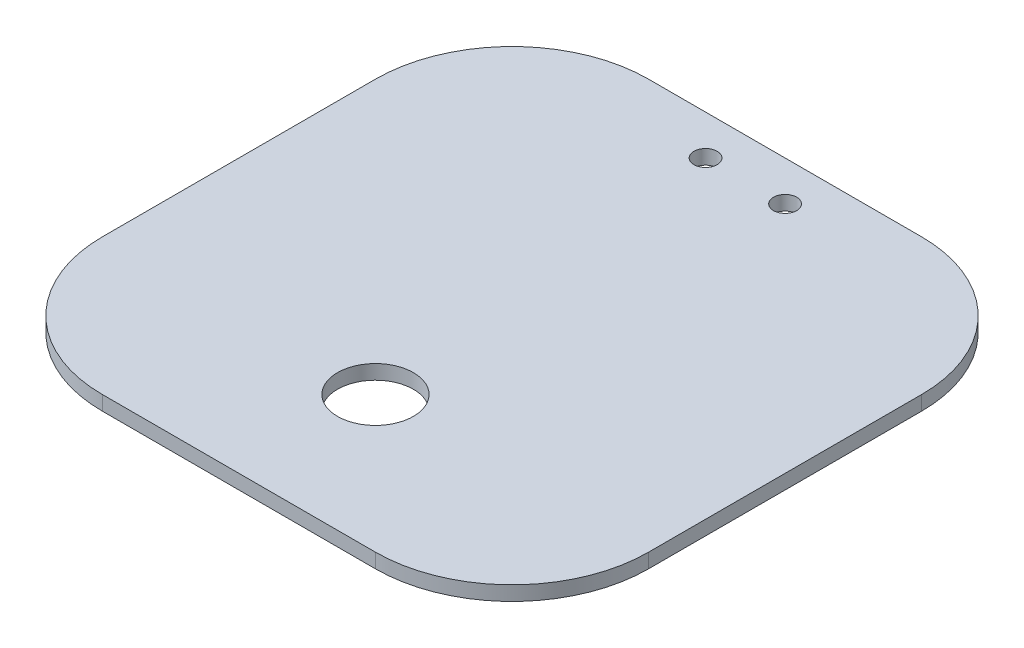
SolidWorks part; units mm, degrees
material "6061-T6 (SS)"
ref_plane "Front" through (0, 0, 0) normal (0, 0, 1) x (1, 0, 0)
ref_plane "Top" through (0, 0, 0) normal (0, 1, 0) x (1, 0, 0)
ref_plane "Right" through (0, 0, 0) normal (1, 0, 0) x (0, 0, -1)
sketch "Sketch1" plane through (0, 0, 0) normal (0, 1, 0) x (1, 0, 0)
  line L1 (-30, 60) -> (30, 60)
  line L2 (-60, 30) -> (-60, -30)
  line L3 (-30, -60) -> (30, -60)
  line L4 (60, 30) -> (60, -30)
  line L5 (-60, 60) -> (60, -60) construction
  line L6 (-60, -60) -> (60, 60) construction
  arc A0 (30, -60) -> (60, -30) centre (30, -30) ccw
  arc A1 (60, 30) -> (30, 60) centre (30, 30) ccw
  arc A2 (-30, 60) -> (-60, 30) centre (-30, 30) ccw
  arc A3 (-60, -30) -> (-30, -60) centre (-30, -30) ccw
  point P0 (0, 0)
  dimension "D3" = 30
  dimension "D1" = 120
  dimension "D2" = 120
extrude "Boss-Extrude1" add sketch "Sketch1" along normal blind 3.175
hole_wizard "#10 Clearance Hole1" positions "Sketch2" profile "Sketch3" hole size "#10" standard "ANSI Inch" end condition through all
sketch "Sketch2" plane through (0, 3.175, 0) normal (0, 1, 0) x (1, 0, 0)
  line L0 (-8.7376, 51.2624) -> (8.7376, 51.2624)
  line L2 (0, 0) -> (0, 51.2624)
  line L3 (30, 60) -> (-30, 60) construction
  point P0 (8.7376, 51.2624)
  point P2 (-8.7376, 51.2624)
  dimension "D1" = 8.7376
  dimension "D2" = 17.4752
sketch "Sketch3" plane through (8.7376, 3.175, -51.2624) normal (1, 0, 0) x (0, 0, 1)
  line L0 (0, 0) -> (0, 3.175)
  line L1 (0, 3.175) -> (2.5527, 3.175)
  line L2 (2.5527, 3.175) -> (2.5527, 0)
  line L5 (2.5527, 0) -> (0, 0)
  line L11 (0, -6.35) -> (0, 107.95) construction
  dimension "Thru Hole Dia." = 5.1054
  dimension "Thru Hole Depth" = 3.175
hole_wizard "5/8 Clearance Hole1" positions "Sketch4" profile "Sketch5" hole size "5/8" standard "ANSI Inch"
sketch "Sketch4" plane through (0, 3.175, 0) normal (0, 1, 0) x (1, 0, 0)
  line L0 (0, -60) -> (0, -30)
  line L1 (-30, -60) -> (30, -60) construction
  line L3 (0, -30) -> (0, 0)
  point P0 (0, -30)
  dimension "D1" = 30
sketch "Sketch5" plane through (0, 3.175, 30) normal (1, 0, 0) x (0, 0, 1)
  line L0 (0, 0) -> (0, 11.8974)
  line L1 (0, 11.8974) -> (8.3337, 6.89)
  line L2 (8.3337, 6.89) -> (8.3337, 0)
  line L5 (8.3337, 0) -> (0, 0)
  line L10 (0, 11.8974) -> (-8.3337, 6.89) construction
  line L11 (0, -6.35) -> (0, 107.95) construction
  dimension "Hole Dia." = 16.6675
  dimension "Hole Depth" = 6.89
  dimension "Drill Angle" = 118
